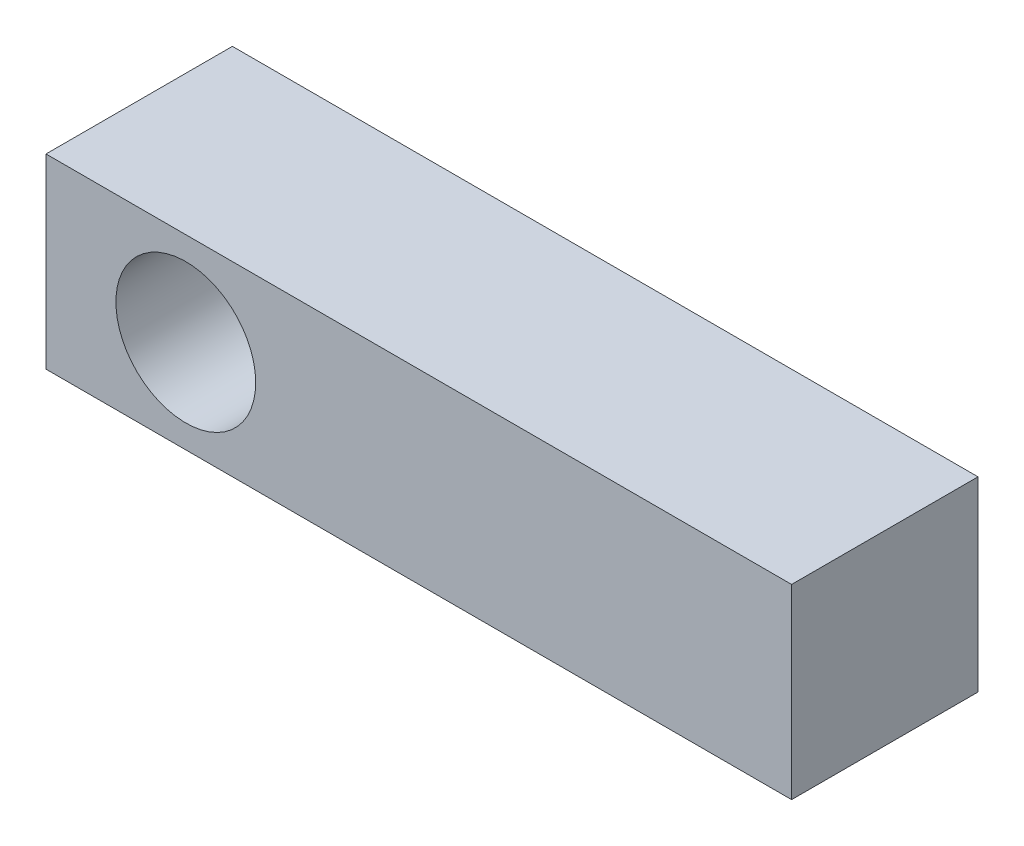
SolidWorks part; units mm, degrees
material "1060 Alloy"
ref_plane "Front Plane" through (0, 0, 0) normal (0, 0, 1) x (1, 0, 0)
ref_plane "Top Plane" through (0, 0, 0) normal (0, 1, 0) x (1, 0, 0)
ref_plane "Right Plane" through (0, 0, 0) normal (1, 0, 0) x (0, 0, -1)
sketch "Sketch1" plane through (0, 0, 0) normal (1, 0, 0) x (0, 0, -1)
  line L1 (-10, -10) -> (10, -10)
  line L2 (-10, -10) -> (-10, 10)
  line L3 (-10, 10) -> (10, 10)
  line L4 (10, -10) -> (10, 10)
  line L5 (-10, -10) -> (10, 10) construction
  line L6 (-10, 10) -> (10, -10) construction
  point P0 (0, 0)
  dimension "D1" = 20
  dimension "D2" = 20
extrude "Boss-Extrude1" add sketch "Sketch1" along normal mid plane 80
sketch "Sketch4" plane through (0, 0, 0) normal (0, 0, 1) x (1, 0, 0)
  line L0 (40, -10) -> (-40, -10) construction
  line L1 (-40, 10) -> (-40, -10) construction
  circle A0 centre (-25, 0) radius 7.5
  dimension "D2" = 15
  dimension "D1" = 10
  dimension "D3" = 15
extrude "Cut-Extrude1" cut sketch "Sketch4" against normal through all both and the other way through all
move or copy body "Body-Move/Copy1" [suppressed] bodies to move or copy 102
